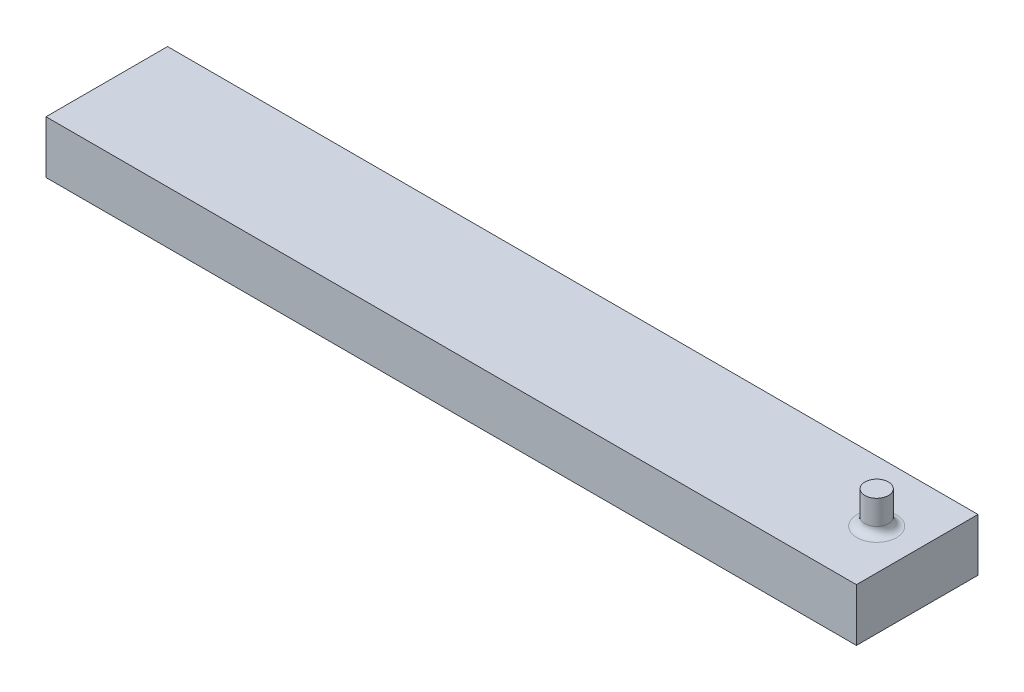
SolidWorks part; units mm, degrees
ref_plane "Front Plane" through (0, 0, 0) normal (0, 0, 1) x (1, 0, 0)
ref_plane "Top Plane" through (0, 0, 0) normal (0, 1, 0) x (1, 0, 0)
ref_plane "Right Plane" through (0, 0, 0) normal (1, 0, 0) x (0, 0, -1)
sketch "Sketch2" plane through (0, 0, 0) normal (0, 1, 0) x (1, 0, 0)
  line L1 (-50, -7.5) -> (50, -7.5)
  line L2 (-50, -7.5) -> (-50, 7.5)
  line L3 (-50, 7.5) -> (50, 7.5)
  line L4 (50, -7.5) -> (50, 7.5)
  line L5 (-50, -7.5) -> (50, 7.5) construction
  line L6 (-50, 7.5) -> (50, -7.5) construction
  point P0 (0, 0)
  dimension "D1" = 100
  dimension "D2" = 15
extrude "Boss-Extrude1" add sketch "Sketch2" along normal mid plane 6.5
sketch "Sketch4" plane through (0, 3.25, 0) normal (0, 1, 0) x (1, 0, 0)
  circle A0 centre (45, 0) radius 1.45
  dimension "D1" = 2.9
extrude "Boss-Extrude2" add sketch "Sketch4" along normal blind 4
sketch "Sketch5" plane through (0, -3.25, 0) normal (0, -1, 0) x (-1, 0, 0)
  circle A0 centre (38.1, 0) radius 5.1
  dimension "D1" = 10.2
extrude "Cut-Extrude1" cut sketch "Sketch5" against normal blind 4
fillet "Fillet1" radius 1 1 edges at (45, 3.25, -1.45)
sketch "Sketch6" plane through (0, 0, 0) normal (0, 0, 1) x (1, 0, 0)
  line L0 (50, -3.25) -> (-50, -3.25) construction
  line L1 (-23.5, -3.25) -> (-15, -3.25)
  line L2 (-23.5, -3.25) -> (-23.5, 0.75)
  line L3 (-23.5, 0.75) -> (-15, 0.75)
  line L4 (-15, -3.25) -> (-15, 0.75)
  line L5 (-15, 0.75) -> (-10, 0.75)
  line L7 (-15, -2.5) -> (-10, -2.5)
  line L8 (-10, 0.75) -> (-10, -2.5)
  line L9 (-50, 3.25) -> (-50, -3.25) construction
  dimension "D1" = 8.5
  dimension "D2" = 5
  dimension "D3" = 3.25
  dimension "D4" = 0.75
  dimension "D5" = 35
  dimension "D6" = 4
extrude "Cut-Extrude3" cut sketch "Sketch6" against normal mid plane 2.25 contours L1 L4 L3 L2 | L8 L5 L4 L7 region at (-19.25, -1.25, 0) region at (-12.5, -0.875, 0)
